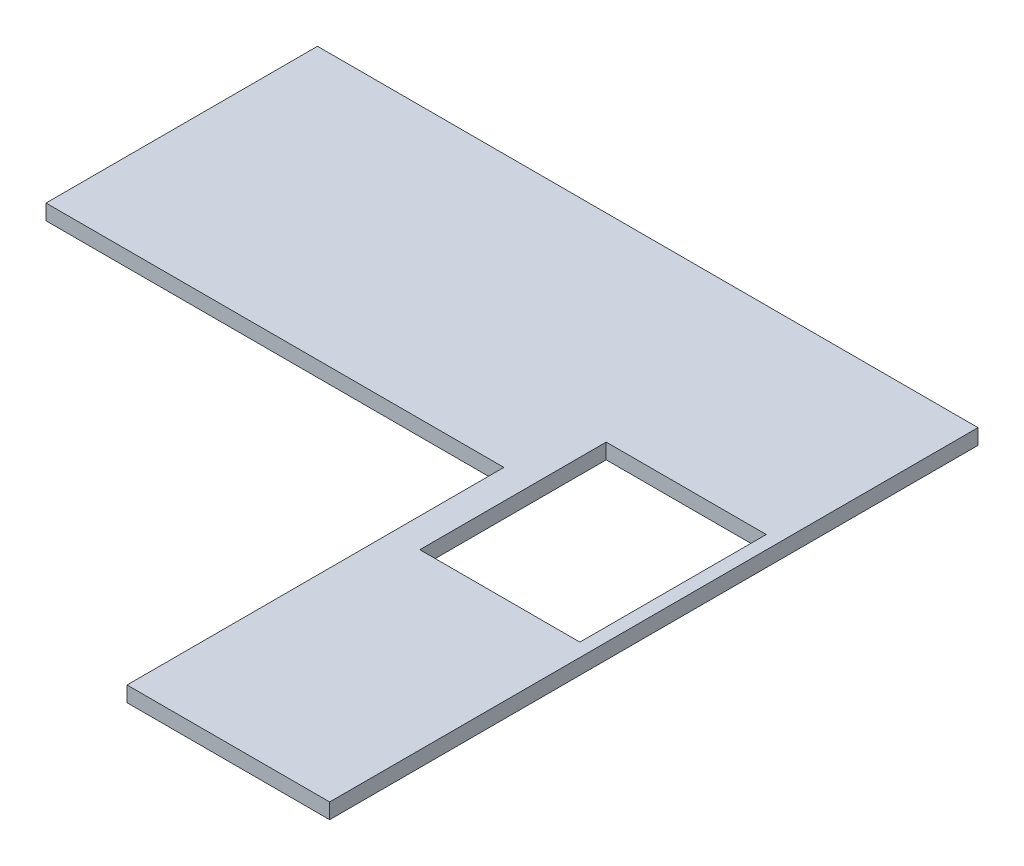
SolidWorks part; units mm, degrees
ref_plane "Спереди" through (0, 0, 0) normal (0, 0, 1) x (1, 0, 0)
ref_plane "Сверху" through (0, 0, 0) normal (0, 1, 0) x (1, 0, 0)
ref_plane "Справа" through (0, 0, 0) normal (1, 0, 0) x (0, 0, -1)
sketch "Эскиз1" plane through (0, 0, 0) normal (0, 1, 0) x (1, 0, 0)
  line L0 (0, 0) -> (0, 670)
  line L1 (0, 670) -> (1630, 670)
  line L2 (1630, 670) -> (1630, -930)
  line L3 (1630, -930) -> (1130, -930)
  line L4 (1130, -930) -> (1130, 0)
  line L5 (1130, 0) -> (0, 0)
  point P3 (0, 0)
  point P8 (0, 0)
  dimension "D1" = 500
  dimension "D2" = 1630
extrude "Бобышка-Вытянуть1" add sketch "Эскиз1" along normal blind 38
sketch "Эскиз2" plane through (0, 38, 0) normal (0, 1, 0) x (1, 0, 0)
  line L1 (1202.1635, 180.3464) -> (1597.1635, 180.3464)
  line L2 (1202.1635, 180.3464) -> (1202.1635, -279.6536)
  line L3 (1202.1635, -279.6536) -> (1597.1635, -279.6536)
  line L4 (1597.1635, 180.3464) -> (1597.1635, -279.6536)
extrude "Вырез-Вытянуть1" cut sketch "Эскиз2" against normal through all
